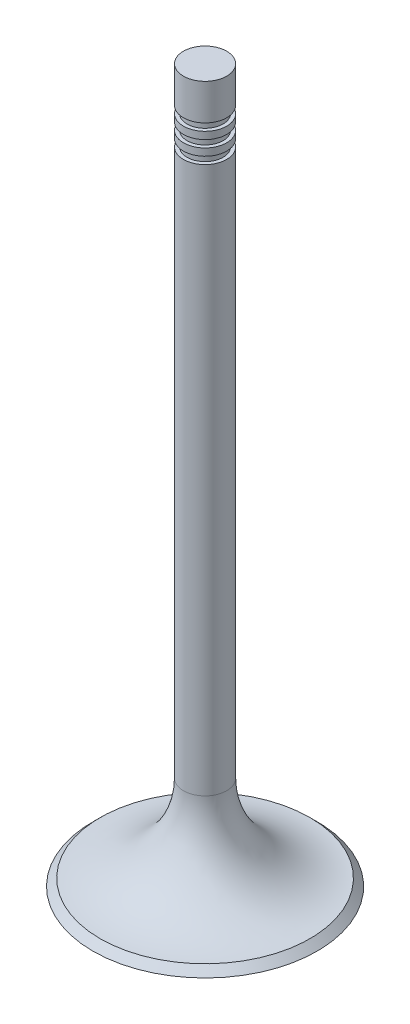
SolidWorks part; units mm, degrees
ref_plane "Front Plane" through (0, 0, 0) normal (0, 0, 1) x (1, 0, 0)
ref_plane "Top Plane" through (0, 0, 0) normal (0, 1, 0) x (1, 0, 0)
ref_plane "Right Plane" through (0, 0, 0) normal (1, 0, 0) x (0, 0, -1)
sketch "Sketch1" plane through (0, 0, 0) normal (0, 1, 0) x (1, 0, 0)
  circle A0 centre (0, 0) radius 15.55
  dimension "D1" = 31.1
extrude "Boss-Extrude1" add sketch "Sketch1" along normal blind 1
chamfer "Chamfer2" distance 1 angle 45 1 edges at (0, 1, 15.55)
sketch "Sketch4" plane through (0, 1, 0) normal (0, 1, 0) x (1, 0, 0)
  circle A0 centre (0, 0) radius 3
  dimension "D1" = 6
extrude "Boss-Extrude2" add sketch "Sketch4" along normal blind 97.8
fillet "Fillet1" radius 12 1 edges at (0, 1, 3)
sketch "Sketch5" plane through (0, 0, 0) normal (0, 0, 1) x (1, 0, 0)
  line L0 (0, 98.8) -> (0, 0) construction
  line L1 (3, 98.8) -> (-3, 98.8) construction
  line L2 (-3, 98.8) -> (-3, 93.8) construction
  line L3 (-3, 98.8) -> (-3, 12.9916) construction
  line L4 (-3, 93.8) -> (-3, 92.8)
  line L5 (-3, 92.8) -> (-3, 91.8)
  line L6 (-3, 91.8) -> (-3, 90.8)
  line L7 (-3, 90.8) -> (-3, 89.8)
  line L8 (-3, 89.8) -> (-3, 88.8)
  line L9 (-3, 88.8) -> (-3, 87.8)
  line L11 (-3, 93.8) -> (-2.5, 93.8)
  line L12 (-3, 93.8) -> (-3, 92.8)
  line L13 (-3, 92.8) -> (-2.5, 92.8)
  line L14 (-2.5, 93.8) -> (-2.5, 92.8)
  line L15 (-3, 91.8) -> (-2.5, 91.8)
  line L16 (-3, 91.8) -> (-3, 90.8)
  line L17 (-3, 90.8) -> (-2.5, 90.8)
  line L18 (-2.5, 91.8) -> (-2.5, 90.8)
  line L19 (-3, 89.8) -> (-2.5, 89.8)
  line L20 (-3, 89.8) -> (-3, 88.8)
  line L21 (-3, 88.8) -> (-2.5, 88.8)
  line L22 (-2.5, 89.8) -> (-2.5, 88.8)
  dimension "D1" = 5
  dimension "D2" = 1
  dimension "D3" = 1
  dimension "D4" = 1
  dimension "D5" = 1
  dimension "D6" = 1
  dimension "D7" = 1
  dimension "D8" = 0.5
revolve "Cut-Revolve1" cut sketch "Sketch5" angle 360 about L0 region at (-2.75, 93.3, 0) region at (-2.75, 89.3, 0) region at (-2.75, 91.3, 0)
